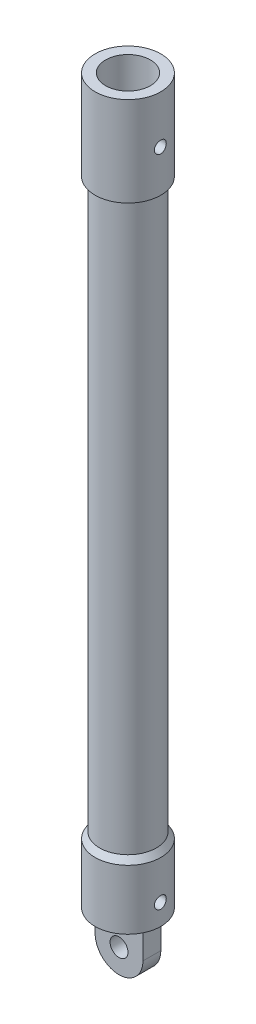
SolidWorks part; units mm, degrees
ref_plane "Front Plane" through (0, 0, 0) normal (0, 0, 1) x (1, 0, 0)
ref_plane "Top Plane" through (0, 0, 0) normal (0, 1, 0) x (1, 0, 0)
ref_plane "Right Plane" through (0, 0, 0) normal (1, 0, 0) x (0, 0, -1)
sketch "Sketch1" plane through (0, 0, 0) normal (0, 0, 1) x (1, 0, 0)
  line L0 (0, 121) -> (0, 0) construction
  line L1 (0, 0) -> (-5.5, 0)
  line L2 (-5.5, 0) -> (-5.5, 10)
  line L3 (-5.5, 10) -> (-4.75, 11)
  line L4 (-4.75, 11) -> (-4.75, 106)
  line L5 (-4.75, 106) -> (-5.5, 106)
  line L6 (-5.5, 106) -> (-5.5, 121)
  line L7 (-5.5, 121) -> (-3.75, 121)
  line L8 (-3.75, 121) -> (-3.75, 2)
  line L9 (-3.75, 2) -> (0, 2)
  line L10 (0, 2) -> (0, 0)
  dimension "D1" = 11
  dimension "D2" = 9.5
  dimension "D3" = 1
  dimension "D4" = 11
  dimension "D5" = 1
  dimension "D6" = 2
  dimension "D7" = 10
  dimension "D8" = 15
  dimension "D9" = 95
revolve "Revolve1" add sketch "Sketch1" angle 360 about L0
sketch "Sketch2" plane through (0, 0, 0) normal (0, 0, 1) x (1, 0, 0)
  line L0 (-4, 0) -> (4, 0)
  line L1 (-5.5, 0) -> (5.5, 0) construction
  line L2 (4, 0) -> (4, -5)
  line L3 (-4, 0) -> (-4, -5)
  line L4 (4, -5) -> (-4, -5) construction
  arc A0 (-4, -5) -> (4, -5) centre (0, -5) ccw
  circle A1 centre (0, -5) radius 1.5
  point P7 (0, 0)
  dimension "D1" = 5
  dimension "D3" = 3
  dimension "D2" = 8
extrude "Boss-Extrude1" add sketch "Sketch2" along normal blind 1.5 and the other way blind 1.5
sketch "Sketch3" plane through (0, 0, 0) normal (1, 0, 0) x (0, 0, -1)
  line L0 (0, 121) -> (0, 0) construction
  line L1 (3.75, 121) -> (-3.75, 121) construction
  line L2 (5.5, 121) -> (-5.5, 121) construction
  line L3 (-5.5, 0) -> (5.5, 0) construction
  circle A0 centre (0, 3.5) radius 1
  circle A1 centre (0, 113) radius 1
  dimension "D1" = 2
  dimension "D2" = 2
  dimension "D3" = 8
  dimension "D4" = 3.5
extrude "Cut-Extrude1" cut sketch "Sketch3" along normal blind 10
